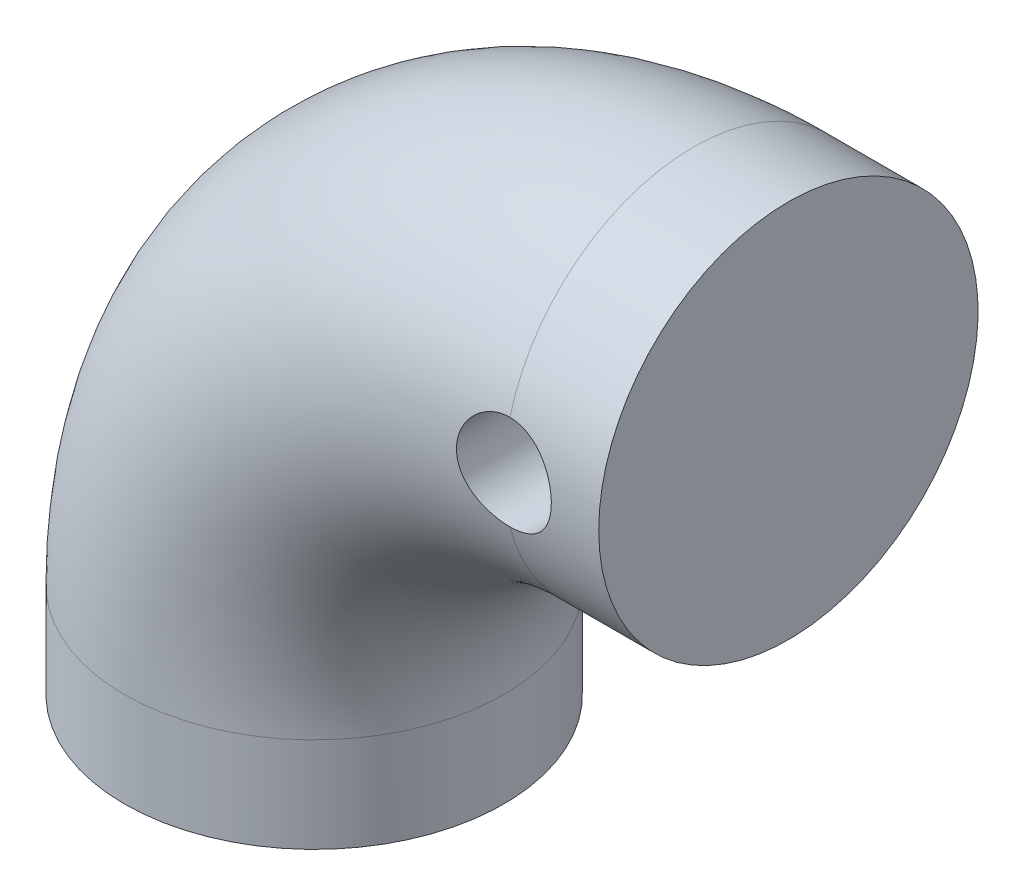
SolidWorks part; units mm, degrees
ref_plane "前视基准面" through (0, 0, 0) normal (0, 0, 1) x (1, 0, 0)
ref_plane "上视基准面" through (0, 0, 0) normal (0, 1, 0) x (1, 0, 0)
ref_plane "右视基准面" through (0, 0, 0) normal (1, 0, 0) x (0, 0, -1)
sketch "草图1" plane through (0, 0, 0) normal (0, 0, 1) x (1, 0, 0)
  line L0 (-32.2646, -7.1007) -> (-32.2646, -3.1007)
  line L1 (-16.2646, 12.8993) -> (-12.2646, 12.8993)
  arc A0 (-32.2646, -3.1007) -> (-16.2646, 12.8993) centre (-16.2646, -3.1007) cw
  point P5 (-32.2646, 12.8993)
  dimension "D3" = 16
  dimension "D1" = 20
  dimension "D2" = 20
sweep "扫描2" add path "草图1" circular profile diameter 16 parameters "D3"=16
sketch "草图19" plane through (0, 0, 0) normal (0, 0, 1) x (1, 0, 0)
  line L3 (-12.2646, 12.8993) -> (-16.2646, 12.8993) construction
  line L4 (-12.2646, 4.8993) -> (-12.2646, 20.8993) construction
  line L5 (-16.2646, 20.8993) -> (-16.2646, 4.8993) construction
  circle A1 centre (-16.2646, 12.8993) radius 2
  point P14 (0, 0)
  dimension "D2" = 4
extrude "切除-拉伸3" cut sketch "草图19" against normal blind 10 and the other way blind 10
